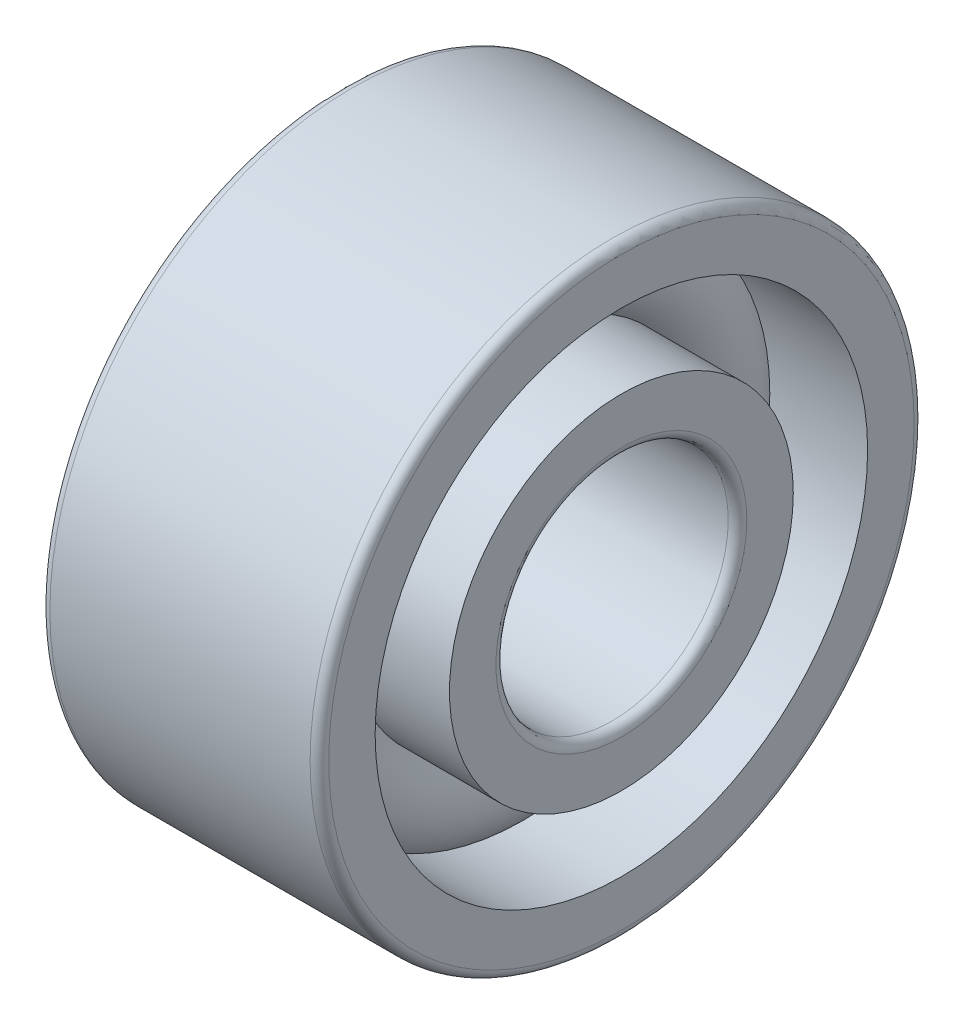
SolidWorks part; units mm, degrees
ref_plane "Plane1" through (0, 0, 0) normal (0, 0, 1) x (1, 0, 0)
ref_plane "Plane2" through (0, 0, 0) normal (0, 1, 0) x (1, 0, 0)
ref_plane "Plane3" through (0, 0, 0) normal (1, 0, 0) x (0, 0, -1)
sketch "Clipboard" plane through (0, 0, 0) normal (0, 0, 1) x (1, 0, 0)
  line L0 (-10, 0) -> (10, 0) construction
  line L1 (0, 0) -> (22.3471, -0.7804)
  line L2 (0, 0) -> (4.4973, 0.157)
  line L3 (0, 0) -> (22.3471, -0.7804)
  line L4 (0, 0) -> (-22.3573, -0.3902)
  dimension "BallCLRad" = 4.5
  dimension "Count" = 2
  dimension "Show_count" = 2
  dimension "Max_count" = 2
  dimension "Min_count" = 1
sketch "CagSpiSke" plane through (0, 0, 0) normal (0, 0, 1) x (1, 0, 0)
  line L0 (0.12, 4.3) -> (0.12, 4.7)
  line L1 (0.12, 4.7) -> (-0.12, 4.7)
  line L2 (-0.12, 4.7) -> (-0.12, 4.3)
  line L3 (-0.12, 4.3) -> (0.12, 4.3)
  line L4 (-20.6375, 0) -> (20.6375, 0) construction
  line L5 (0, 0) -> (0, 23.7692) construction
  dimension "Thickness" = 0.24
  dimension "OD" = 9.4
  dimension "ID" = 8.6
revolve "CageSpine" add sketch "CagSpiSke" angle 0.001 about L4 reverse direction yes
ref_axis "Axis1" through (-50, 0, 0) along (1, 0, 0)
sketch "CagBalSke" plane through (0, 0, 0) normal (0, 0, 1) x (1, 0, 0)
  line L0 (-1.32, 4.5) -> (1.32, 4.5)
  line L1 (-1.905, 4.5) -> (1.905, 4.5) construction
  line L2 (-10, 0) -> (10, 0) construction
  line L3 (0, 0) -> (0, 24) construction
  arc A0 (1.32, 4.5) -> (-1.32, 4.5) centre (0, 4.5) cw
  dimension "CageWallOD" = 2.64
  dimension "BallCLRad" = 4.5
revolve "CageBall" [suppressed] add sketch "CagBalSke" angle 360 about L1 reverse direction yes
pattern_circular "CageBalls" [suppressed] count 2 every 180 about axis through (-50, 0, 0) along (1, 0, 0)
sketch "CagTrmODSke" plane through (0, 0, 0) normal (0, 0, 1) x (1, 0, 0)
  line L0 (1.321, 4.7) -> (1.321, 5.821)
  line L1 (1.321, 5.821) -> (-1.321, 5.821)
  line L2 (-1.321, 5.821) -> (-1.321, 4.7)
  line L3 (-1.321, 4.7) -> (1.321, 4.7)
  line L4 (-20.6375, 0) -> (20.6375, 0) construction
  line L5 (0, 0) -> (0, 25) construction
  dimension "Width" = 2.642
  dimension "ID" = 9.4
  dimension "OD" = 11.642
revolve "CageTrimOD" [suppressed] cut sketch "CagTrmODSke" angle 360 about L4 reverse direction yes
sketch "CagTrmIDSke" plane through (0, 0, 0) normal (0, 0, 1) x (1, 0, 0)
  line L0 (1.321, 3.181) -> (1.321, 4.3)
  line L1 (1.321, 4.3) -> (-1.321, 4.3)
  line L2 (-1.321, 4.3) -> (-1.321, 3.181)
  line L3 (-1.321, 3.181) -> (1.321, 3.181)
  line L4 (-20.6375, 0) -> (20.6375, 0) construction
  line L5 (0, 0) -> (0, 25) construction
  dimension "ID" = 6.362
  dimension "OD" = 8.6
  dimension "Width" = 2.642
revolve "CageTrimID" [suppressed] cut sketch "CagTrmIDSke" angle 360 about L4 reverse direction yes
sketch "BalSimSke" plane through (0, 0, 0) normal (0, 0, 1) x (1, 0, 0)
  line L0 (-10, 0) -> (10, 0) construction
  line L1 (-10, 4.5) -> (10, 4.5) construction
  line L2 (0, 0) -> (0, 23) construction
  circle A0 centre (0, 4.5) radius 1.2
  dimension "Ball_diameter" = 2.4
  dimension "BallCLRad" = 4.5
revolve "BallsSimplified" add sketch "BalSimSke" angle 360 about L0
sketch "BalDetSke" plane through (0, 0, 0) normal (0, 0, 1) x (1, 0, 0)
  line L0 (-1.2, 4.5) -> (1.2, 4.5)
  line L1 (-1.905, 4.5) -> (1.905, 4.5) construction
  line L2 (0, 0) -> (0, 25) construction
  arc A0 (1.2, 4.5) -> (-1.2, 4.5) centre (0, 4.5) cw
  dimension "Ball_diameter" = 2.4
  dimension "BallCLRad" = 4.5
revolve "BallDetailed" [suppressed] add sketch "BalDetSke" angle 360 about L1 reverse direction yes
sketch "InnRacSke" plane through (0, 0, 0) normal (0, 0, 1) x (1, 0, 0)
  line L0 (-0.8606, 3.7) -> (-3, 3.7)
  line L1 (-3, 3.7) -> (-3, 2.7)
  line L2 (-2.8, 2.5) -> (2.8, 2.5)
  line L3 (3, 2.7) -> (3, 3.7)
  line L4 (3, 3.7) -> (0.8606, 3.7)
  line L5 (-20.6375, 0) -> (20.6375, 0) construction
  line L6 (0, 0) -> (0, 30) construction
  arc A0 (-3, 2.7) -> (-2.8, 2.5) centre (-2.8, 2.7) ccw
  arc A1 (2.8, 2.5) -> (3, 2.7) centre (2.8, 2.7) ccw
  arc A2 (0.8606, 3.7) -> (-0.8606, 3.7) centre (0, 4.5) cw
  dimension "Fillet_radius" = 0.2
  dimension "Ball_diameter" = 2.35
  dimension "ID" = 5
  dimension "OD" = 7.4
  dimension "Width" = 6
  dimension "BallCLRad" = 4.5
revolve "InnerRace" add sketch "InnRacSke" angle 360 about L5 reverse direction yes
sketch "OutRacSke" plane through (0, 0, 0) normal (0, 0, 1) x (1, 0, 0)
  line L0 (-0.8606, 5.3) -> (-3, 5.3)
  line L1 (-3, 5.3) -> (-3, 6.3)
  line L2 (-2.8, 6.5) -> (2.8, 6.5)
  line L3 (3, 6.3) -> (3, 5.3)
  line L4 (3, 5.3) -> (0.8606, 5.3)
  line L5 (-20.6375, 0) -> (20.6375, 0) construction
  line L6 (0, 0) -> (0, 30) construction
  arc A0 (-3, 6.3) -> (-2.8, 6.5) centre (-2.8, 6.3) cw
  arc A1 (2.8, 6.5) -> (3, 6.3) centre (2.8, 6.3) cw
  arc A2 (0.8606, 5.3) -> (-0.8606, 5.3) centre (0, 4.5) ccw
  dimension "Fillet_radius" = 0.2
  dimension "Ball_diameter" = 2.35
  dimension "OD" = 13
  dimension "ID" = 10.6
  dimension "Width" = 6
  dimension "BallCLRad" = 4.5
revolve "OuterRace" add sketch "OutRacSke" angle 360 about L5 reverse direction yes
pattern_circular "BallsDetailed" [suppressed] count 2 every 180 about axis through (-50, 0, 0) along (1, 0, 0)
equation "\"BallCLRad@Clipboard\" = ( \"OD@OutRacSke\" + \"ID@InnRacSke\" ) / 4"
equation "\"BallCLRad@BalSimSke\" = \"BallCLRad@Clipboard\""
equation "\"BallCLRad@BalDetSke\" = \"BallCLRad@Clipboard\""
equation "\"BallCLRad@InnRacSke\" = \"BallCLRad@Clipboard\""
equation "\"BallCLRad@OutRacSke\" = \"BallCLRad@Clipboard\""
equation "\"Ball_diameter@InnRacSke\" = \"Ball_diameter@BalDetSke\" - 0.05"
equation "\"Ball_diameter@OutRacSke\" = \"Ball_diameter@BalDetSke\" - 0.05"
equation "\"Ball_diameter@BalSimSke\" = \"Ball_diameter@BalDetSke\""
equation "\"Width@OutRacSke\" = \"Width@InnRacSke\""
equation "\"Fillet_radius@OutRacSke\" = \"Fillet_radius@InnRacSke\""
equation "\"Max_count@Clipboard\" = int( 3.14159265 / atn(( \"Ball_diameter@BalDetSke\" / 2) / sqr( \"BallCLRad@Clipboard\"  *  \"BallCLRad@Clipboard\" - ( \"Ball_diameter@BalDetSke\" / 2) *  ( \"Ball_diameter@BalDetSke\" / 2))))"
equation "\"Max_count@Clipboard\" = ((sgn( \"Max_count@Clipboard\" - \"Count@Clipboard\" )-1)*( \"Max_count@Clipboard\" - \"Count@Clipboard\" ))/-2+ \"Count@Clipboard\""
equation "\"Count@BallsDetailed\" = int( \"Show_count@Clipboard\" ) "
equation "\"Count@BallsDetailed\" = ((sgn( \"Count@BallsDetailed\" - \"Max_count@Clipboard\" )-1)*( \"Count@BallsDetailed\" - \"Max_count@Clipboard\" ))/-2+ \"Max_count@Clipboard\""
equation "\"Count@BallsDetailed\" = ((sgn( \"Count@BallsDetailed\" - \"Min_count@Clipboard\" )+1)*( \"Count@BallsDetailed\" - \"Min_count@Clipboard\"))/2 +\"Min_count@Clipboard\""
equation "\"Angle@BallsDetailed\" = 360.0 / \"Max_count@Clipboard\""
equation "\"BallCLRad@CagBalSke\" = \"BallCLRad@Clipboard\""
equation "\"Count@CageBalls\" = \"Count@BallsDetailed\""
equation "\"Angle@CageBalls\" = \"Angle@BallsDetailed\""
equation "\"Angle@CageSpine\" =  \"Angle@CageBalls\" * ( \"Count@CageBalls\" -1 + int( \"Count@CageBalls\" / \"Max_count@Clipboard\" ) )  + 0.001 -  int( \"Count@CageBalls\" / \"Max_count@Clipboard\" ) * 0.001"
equation "\"Angle@CageSpine\" =  \"Angle@CageSpine\" * int( \"Min_count@Clipboard\" / 2) + int(1 / \"Min_count@Clipboard\")  * 0.001"
equation "\"CageWallOD@CagBalSke\" =  \"Ball_diameter@BalDetSke\" * 1.1"
equation "\"Thickness@CagSpiSke\" =  \"Ball_diameter@BalDetSke\" * 0.1"
equation "\"OD@CagTrmODSke\" = \"BallCLRad@Clipboard\" * 2 + \"CageWallOD@CagBalSke\" + 0.002"
equation "\"ID@CagTrmODSke\" = \"BallCLRad@Clipboard\" * 2 + \"Ball_diameter@BalDetSke\" / 6"
equation "\"OD@CagTrmIDSke\" = \"BallCLRad@Clipboard\" * 2 - \"Ball_diameter@BalDetSke\" / 6"
equation "\"ID@CagTrmIDSke\" = \"BallCLRad@Clipboard\" * 2 - \"CageWallOD@CagBalSke\" + 0.002"
equation "\"OD@CagSpiSke\" = \"ID@CagTrmODSke\""
equation "\"ID@CagSpiSke\" = \"OD@CagTrmIDSke\""
equation "\"Width@CagTrmODSke\" = \"CageWallOD@CagBalSke\" + 0.002"
equation "\"Width@CagTrmIDSke\" = \"CageWallOD@CagBalSke\" + 0.002"
